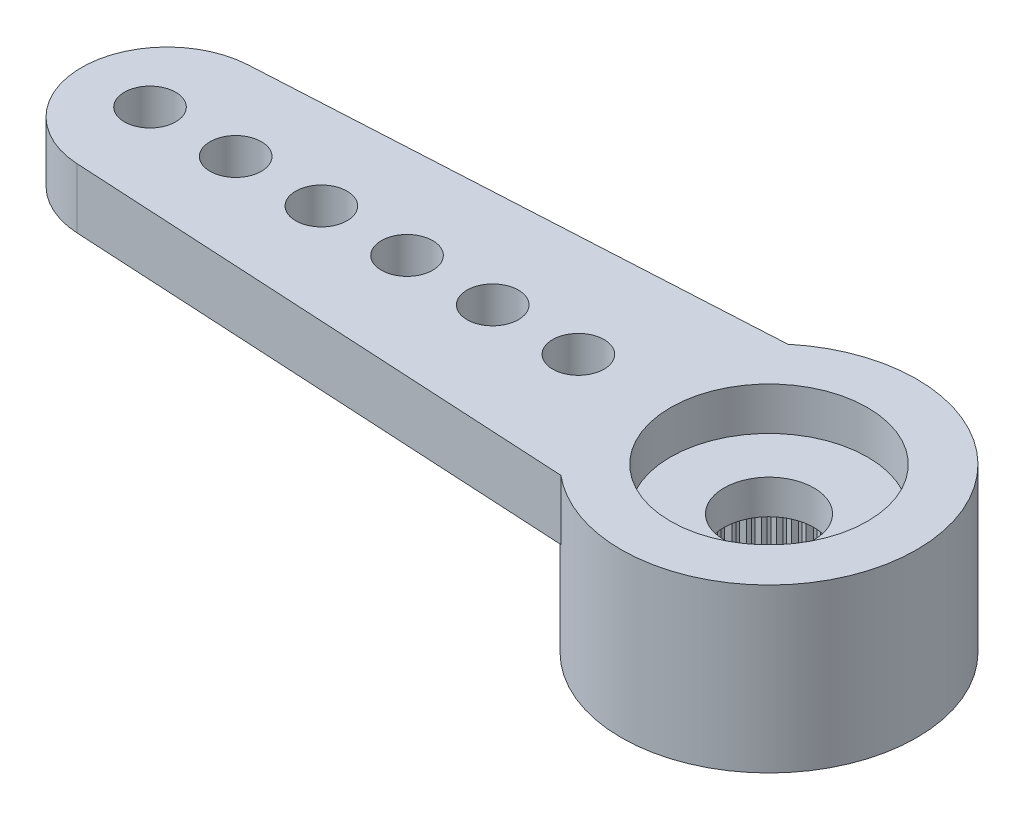
SolidWorks part; units mm, degrees
material "PVC Rígido"
ref_plane "Plano frontal" through (0, 0, 0) normal (0, 0, 1) x (1, 0, 0)
ref_plane "Plano superior" through (0, 0, 0) normal (0, 1, 0) x (1, 0, 0)
ref_plane "Plano direito" through (0, 0, 0) normal (1, 0, 0) x (0, 0, -1)
sketch "Esboço1" plane through (0, 0, 0) normal (0, 1, 0) x (1, 0, 0)
  line L0 (0, 0) -> (-14.05, 0) construction
  line L1 (-14.1591, 1.997) -> (-2.2091, 2.65)
  line L2 (-2.2091, -2.65) -> (-14.1591, -1.997)
  arc A0 (-2.2091, -2.65) -> (-2.2091, 2.65) centre (0, 0) ccw
  arc A1 (-14.1591, 1.997) -> (-14.1591, -1.997) centre (-14.05, 0) ccw
  dimension "D1" = 6.9
  dimension "D2" = 4
  dimension "D3" = 19.5
  dimension "D4" = 5.3
extrude "Ressalto-extrusão1" add sketch "Esboço1" against normal blind 1.4
sketch "Esboço2" plane through (0, -1.4, 0) normal (0, -1, 0) x (1, 0, 0)
  arc A0 (-2.2091, -2.65) -> (-2.2091, 2.65) centre (0, 0) ccw construction
  circle A1 centre (0, 0) radius 3.45
extrude "Ressalto-extrusão2" add sketch "Esboço2" along normal offset from surface (2.4 mm away) 3.8 up to face at (-7.242, 0, 0)
hole_wizard "Furo4" positions "Esboço9" profile "Esboço10" legacy end condition through all
sketch "Esboço9" plane through (0, 0, 0) normal (0, 1, 0) x (1, 0, 0)
  line L1 (-14.45, 0) -> (0, 0) construction
  arc A2 (-14.1591, 1.997) -> (-14.1591, -1.997) centre (-14.05, 0) ccw construction
  point P0 (-14.45, 0)
  point P19 (-16.05, 0)
  dimension "D1" = 1.6
sketch "Esboço10" plane through (-14.45, 0, 0) normal (1, 0, 0) x (0, 0, 1)
  line L0 (0, 0) -> (0, 3.8)
  line L1 (0, 3.8) -> (0.6, 3.8)
  line L2 (0.6, 3.8) -> (0.6, 0)
  line L3 (0.6, 0) -> (0, 0)
  line L4 (0, 110) -> (0, -10) construction
  dimension "Diameter" = 1.2
  dimension "Depth" = 3.8
pattern_linear "Padrão linear1" count 6 spacing 2 along (1, 0, 0) of "Furo4"
hole_wizard "Furo1" positions "Esboço3" profile "Esboço4" legacy
sketch "Esboço3" plane through (0, -3.8, 0) normal (0, -1, 0) x (-1, 0, 0)
  point P0 (0, 0)
sketch "Esboço4" plane through (0, -3.8, 0) normal (1, 0, 0) x (0, 0, -1)
  line L0 (0, 0) -> (0, 2)
  line L1 (0, 2) -> (2.475, 2)
  line L2 (2.475, 2) -> (2.475, 0)
  line L3 (2.475, 0) -> (0, 0)
  line L4 (0, 110) -> (0, -10) construction
  dimension "Diameter" = 4.95
  dimension "Depth" = 2
hole_wizard "Furo2" positions "Esboço5" profile "Esboço6" legacy
sketch "Esboço5" plane through (0, 0, 0) normal (0, 1, 0) x (1, 0, 0)
  point P0 (0, 0)
sketch "Esboço6" plane through (0, 0, 0) normal (1, 0, 0) x (0, 0, 1)
  line L0 (0, 0) -> (0, 1)
  line L1 (0, 1) -> (2.3, 1)
  line L2 (2.3, 1) -> (2.3, 0)
  line L3 (2.3, 0) -> (0, 0)
  line L4 (0, 110) -> (0, -10) construction
  dimension "Diameter" = 4.6
  dimension "Depth" = 1
hole_wizard "Furo3" positions "Esboço7" profile "Esboço8" legacy end condition through all
sketch "Esboço7" plane through (0, 0, 0) normal (0, 1, 0) x (1, 0, 0)
  point P0 (0, 0)
sketch "Esboço8" plane through (0, 0, 0) normal (1, 0, 0) x (0, 0, 1)
  line L0 (0, 0) -> (0, 3.8)
  line L1 (0, 3.8) -> (1.05, 3.8)
  line L2 (1.05, 3.8) -> (1.05, 0)
  line L3 (1.05, 0) -> (0, 0)
  line L4 (0, 110) -> (0, -10) construction
  dimension "Diameter" = 2.1
  dimension "Depth" = 3.8
sketch "Esboço11" plane through (0, -3.8, 0) normal (0, -1, 0) x (1, 0, 0)
  line L0 (-0.0981, 2.4731) -> (0, 2.375)
  line L1 (0, 2.375) -> (0.0981, 2.4731)
  line L2 (0, 0) -> (0, 2.475) construction
  circle A0 centre (0, 0) radius 2.375 construction
  circle A1 centre (0, 0) radius 2.475
  arc A2 (0.0981, 2.4731) -> (-0.0981, 2.4731) centre (0, 0) ccw
  dimension "D3" = 4.75
  dimension "D2" = 0.1
  dimension "D1" = 0
extrude "Ressalto-extrusão3" add sketch "Esboço11" against normal up to surface (2 mm away) up to face at (0, -1.8, 1.05)
pattern_circular "PadrãoCircular1" count 60 over 360 about axis through (0, -1.4, 0) along (0, 1, 0) of "Ressalto-extrusão3"
ref_axis "Axis1" through (0, -1, 0) along (0, 1, 0)
